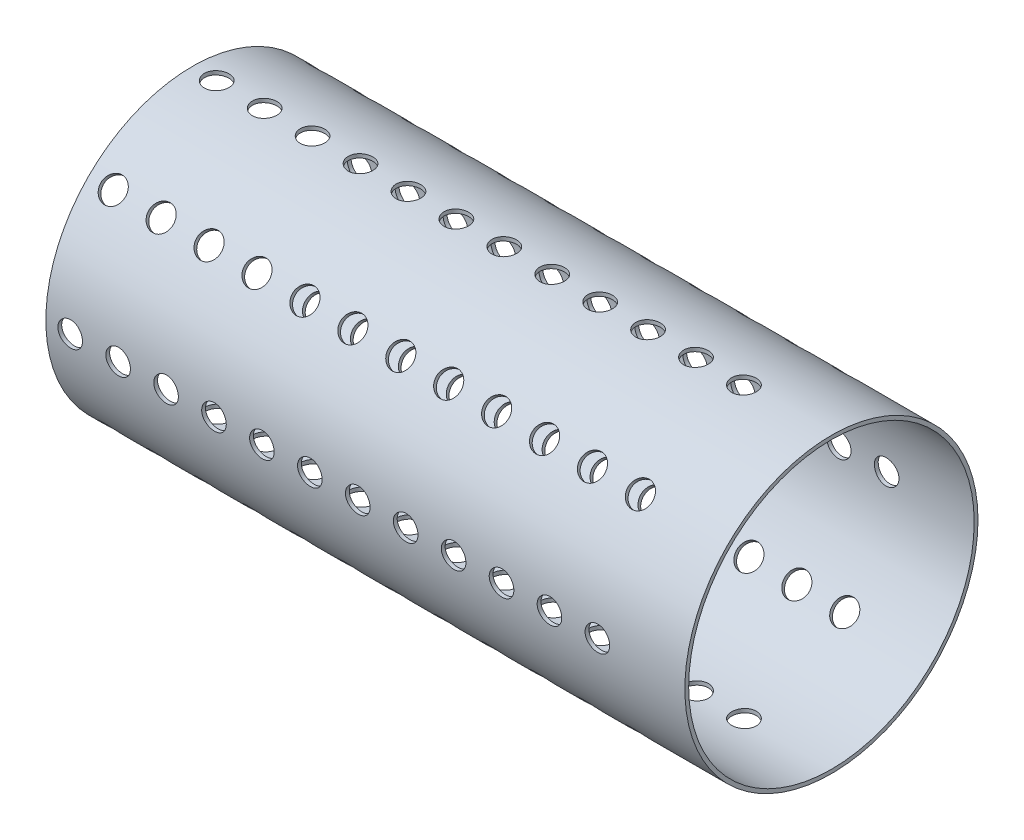
SolidWorks part; units mm, degrees
ref_plane "Front Plane" through (0, 0, 0) normal (0, 0, 1) x (1, 0, 0)
ref_plane "Top Plane" through (0, 0, 0) normal (0, 1, 0) x (1, 0, 0)
ref_plane "Right Plane" through (0, 0, 0) normal (1, 0, 0) x (0, 0, -1)
sketch "Sketch1" plane through (0, 0, 0) normal (1, 0, 0) x (0, 0, -1)
  circle A0 centre (0, 0) radius 23.3045
  circle A1 centre (0, 0) radius 22.6974
  dimension "D1" = 46.609
  dimension "D2" = 0.6071
extrude "Boss-Extrude1" add sketch "Sketch1" along normal blind 101.6
sketch "Sketch3" plane through (0, 0, 0) normal (0, 1, 0) x (1, 0, 0)
  line L0 (4.6468, 0) -> (109.4742, 0) construction
sketch "Sketch2" plane through (0, 0, 0) normal (0, 0, 1) x (1, 0, 0)
  line L0 (0, 0) -> (105.98, 0) construction
  circle A0 centre (3.8703, 0) radius 1.9564
  circle A1 centre (11.4903, 0) radius 1.9564
  circle A2 centre (19.1103, 0) radius 1.9564
  circle A3 centre (26.7303, 0) radius 1.9564
  circle A4 centre (34.3503, 0) radius 1.9564
  circle A5 centre (41.9703, 0) radius 1.9564
  circle A6 centre (49.5903, 0) radius 1.9564
  circle A7 centre (57.2103, 0) radius 1.9564
  circle A8 centre (64.8303, 0) radius 1.9564
  circle A9 centre (72.4503, 0) radius 1.9564
  circle A10 centre (80.0703, 0) radius 1.9564
  circle A11 centre (87.6903, 0) radius 1.9564
  dimension "D1" = 12
extrude "Cut-Extrude1" cut sketch "Sketch2" against normal through all and the other way through all
pattern_circular "CirPattern1" count 8 over 360 about axis through (4.6468, 0, 0) along (1, 0, 0) of "Cut-Extrude1"
